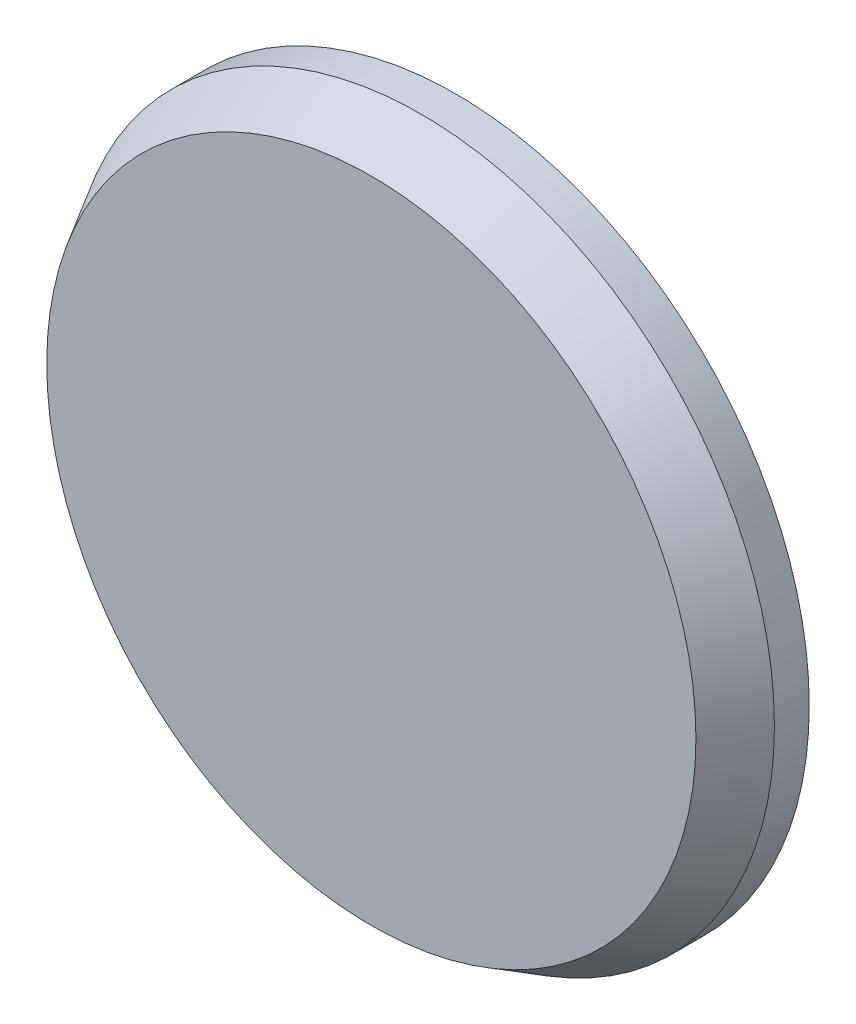
SolidWorks part; units mm, degrees
ref_plane "Přední rovina" through (0, 0, 0) normal (0, 0, 1) x (1, 0, 0)
ref_plane "Horní rovina" through (0, 0, 0) normal (0, 1, 0) x (1, 0, 0)
ref_plane "Pravá rovina" through (0, 0, 0) normal (1, 0, 0) x (0, 0, -1)
sketch "Sketch1" plane through (0, 0, 0) normal (0, 0, 1) x (1, 0, 0)
  circle A0 centre (0, 0) radius 17.75
  dimension "D1" = 35.5
extrude "Boss-Extrude1" add sketch "Sketch1" along normal blind 4.25
sketch "Sketch2" plane through (0, 0, 0) normal (0, 0, -1) x (-1, 0, 0)
  line L9 (14.5045, -1.15) -> (1.15, -1.15)
  line L10 (1.15, -1.15) -> (1.15, -14.5045)
  line L11 (-1.15, -14.5045) -> (-1.15, -1.15)
  line L12 (-1.15, -1.15) -> (-14.5045, -1.15)
  line L13 (-14.5045, 1.15) -> (-1.15, 1.15)
  line L14 (-1.15, 1.15) -> (-1.15, 14.5045)
  line L15 (1.15, 14.5045) -> (1.15, 1.15)
  line L16 (1.15, 1.15) -> (14.5045, 1.15)
  line L17 (-1.15, 14.5045) -> (1.15, 14.5045)
  line L18 (14.5045, 1.15) -> (14.5045, -1.15)
  line L19 (1.15, -14.5045) -> (-1.15, -14.5045)
  line L20 (-14.5045, -1.15) -> (-14.5045, 1.15)
  circle A9 centre (0, 0) radius 14.55
  circle A10 centre (0, 0) radius 17.75 construction
  arc A13 (1.15, -14.5045) -> (14.5045, -1.15) centre (0, 0) ccw
  arc A14 (-14.5045, -1.15) -> (-1.15, -14.5045) centre (0, 0) ccw
  arc A15 (-1.15, 14.5045) -> (-14.5045, 1.15) centre (0, 0) ccw
  arc A16 (14.5045, 1.15) -> (1.15, 14.5045) centre (0, 0) ccw
  dimension "D1" = 14.55
  dimension "D2" = 2.3
  dimension "D3" = 2.3
extrude "Cut-Extrude1" cut sketch "Sketch2" against normal blind 2.75 contours L20 L12 L11 L19 L10 L9 L18 L16 L15 L17 L14 L13 region at (0, 0, 0)
chamfer "Chamfer1" distance 2.5 angle 30 1 edges at (17.75, 0, 4.25) first distance on face at (17.75, 0, 4.25)
